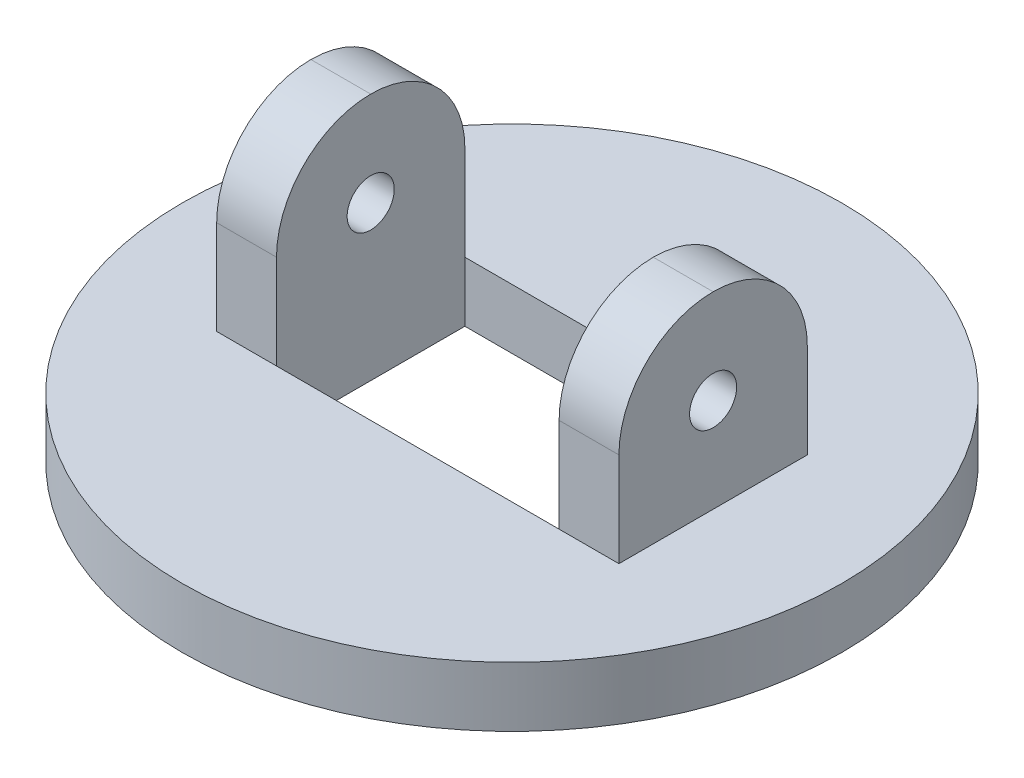
SolidWorks part; units mm, degrees
ref_plane "Front Plane" through (0, 0, 0) normal (0, 0, 1) x (1, 0, 0)
ref_plane "Top Plane" through (0, 0, 0) normal (0, 1, 0) x (1, 0, 0)
ref_plane "Right Plane" through (0, 0, 0) normal (1, 0, 0) x (0, 0, -1)
sketch "Sketch1" plane through (0, 0, 0) normal (0, 1, 0) x (1, 0, 0)
  line L1 (-15, -10) -> (15, -10)
  line L2 (-15, -10) -> (-15, 10)
  line L3 (-15, 10) -> (15, 10)
  line L4 (15, -10) -> (15, 10)
  line L5 (-15, -10) -> (15, 10) construction
  line L6 (-15, 10) -> (15, -10) construction
  circle A0 centre (0, 0) radius 35
  dimension "D2" = 70
  dimension "D1" = 30
  dimension "D3" = 20
extrude "Boss-Extrude1" add sketch "Sketch1" along normal blind 6.35
sketch "Sketch2" plane through (0, 6.35, 0) normal (0, 1, 0) x (1, 0, 0)
  line L0 (-15, -10) -> (15, -10) construction
  line L1 (-15, 10) -> (-21.35, 10)
  line L2 (-15, 10) -> (-15, -10)
  line L3 (-15, -10) -> (-21.35, -10)
  line L4 (-21.35, 10) -> (-21.35, -10)
  line L5 (0, 0) -> (0, -10) construction
  line L6 (15, -10) -> (21.35, -10)
  line L7 (21.35, 10) -> (21.35, -10)
  line L8 (15, 10) -> (21.35, 10)
  line L9 (15, 10) -> (15, -10)
  dimension "D1" = 6.35
extrude "Boss-Extrude2" add sketch "Sketch2" along normal blind 20
sketch "Sketch3" plane through (21.35, 0, 0) normal (1, 0, 0) x (0, 0, -1)
  line L0 (-10, 6.35) -> (10, 6.35) construction
  circle A0 centre (0, 16.35) radius 2.5
  dimension "D1" = 5
  dimension "D2" = 10
extrude "Cut-Extrude1" cut sketch "Sketch3" against normal blind 57
fillet "Fillet1" radius 10 4 edges at (18.175, 26.35, -10) (18.175, 26.35, 10) (-18.175, 26.35, -10) (-18.175, 26.35, 10)
